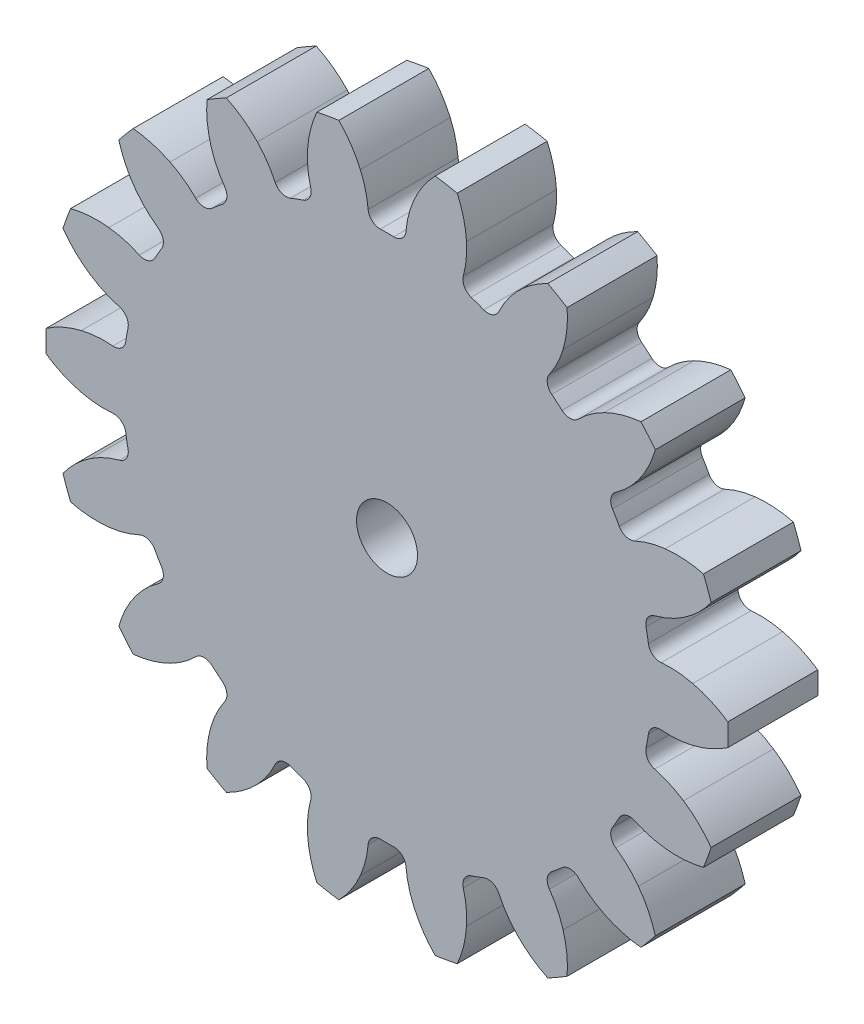
SolidWorks part; units mm, degrees
ref_plane "Front" through (0, 0, 0) normal (0, 0, 1) x (1, 0, 0)
ref_plane "Top" through (0, 0, 0) normal (0, 1, 0) x (1, 0, 0)
ref_plane "Right" through (0, 0, 0) normal (1, 0, 0) x (0, 0, -1)
sketch "Sketch1" plane through (0, 0, 0) normal (0, 0, 1) x (1, 0, 0)
  line L0 (0, 0) -> (19.939, 0) construction
  line L1 (19.939, 0) -> (22.1544, 0) construction
  circle A0 centre (0, 0) radius 19.939 construction
  circle A1 centre (0, 0) radius 22.1544
  dimension "pitch_diameter" = 39.878
  dimension "addendum" = 2.2154
extrude "GEAR_BASE" add sketch "Sketch1" along normal mid plane 5.842
sketch "Sketch2" plane through (0, 0, 2.921) normal (0, 0, 1) x (1, 0, 0)
  line L0 (0, 0) -> (17.1697, 0) construction
  line L1 (17.1697, 0) -> (19.939, 0) construction
  line L2 (0, 0) -> (-22.1544, 0) construction
  line L3 (0, 0) -> (-20.8184, -7.5773) construction
  line L4 (-21.0554, -6.8914) -> (-19.2602, -5.1582) construction
  line L5 (-19.2602, -5.1582) -> (-16.6935, -4.0158) construction
  line L6 (-22.1426, -0.7256) -> (-19.8629, -1.7402) construction
  line L7 (-19.8629, -1.7402) -> (-17.0602, -1.9359) construction
  line L8 (-18.665, -6.7935) -> (-19.2602, -5.1582) construction
  line L9 (-19.8629, -1.7402) -> (-19.8629, 0) construction
  line L12 (0, 0) -> (-19.8629, -1.7402) construction
  line L13 (0, 0) -> (-19.2602, -5.1582) construction
  line L14 (-19.2602, -5.1582) -> (-16.762, -14.4864) construction
  line L15 (-19.8629, -1.7402) -> (-20.7057, 7.8798) construction
  line L16 (-19.2602, -5.1582) -> (-19.8629, -1.7402) construction
  line L17 (-16.9088, -2.9815) -> (-17.0602, -1.9359) construction
  line L18 (-16.9088, -2.9815) -> (-16.6935, -4.0158) construction
  circle A0 centre (0, 0) radius 19.939 construction
  circle A1 centre (0, 0) radius 17.1697 construction
  circle A2 centre (0, 0) radius 22.1544 construction
  arc A3 (-21.0554, -6.8914) -> (-22.1426, -0.7256) centre (0, 0) cw
  arc A4 (-16.6935, -4.0158) -> (-17.0602, -1.9359) centre (0, 0) cw construction
  arc A6 (-21.0554, -6.8914) -> (-19.2602, -5.1582) centre (-15.4012, -10.9516) cw
  arc A7 (-22.1426, -0.7256) -> (-19.8629, -1.7402) centre (-18.2181, 5.0236) ccw
  arc A8 (-19.2602, -5.1582) -> (-17.3885, -4.3144) centre (-15.7761, -10.3888) cw
  arc A9 (-19.8629, -1.7402) -> (-17.8155, -1.893) centre (-18.3779, 4.3666) ccw
  arc A10 (-17.3885, -4.3144) -> (-16.8275, -3.4109) centre (-17.5874, -3.565) ccw
  arc A11 (-17.8155, -1.893) -> (-16.9793, -2.5501) centre (-17.7461, -2.6653) cw
  arc A12 (-16.8275, -3.4109) -> (-16.9793, -2.5501) centre (0, 0) cw
  dimension "base_fillet" = 0.7754
  dimension "D12" = 6.9609
  dimension "deddendum" = 2.7693
  dimension "D3" = 20
  dimension "D4" = 1.7402
  dimension "D5" = 1.7402
  dimension "D11" = 3.4707
  dimension "Pressure_Angle" = 20
  dimension "D14" = 9
  dimension "D15" = 9
extrude "GEAR_CUT" cut sketch "Sketch2" against normal through all
ref_axis "GEAR_AXIS" through (0, 0, 50) along (0, 0, -1)
pattern_circular "GEAR_TEETH" count 18 over 360 about axis through (0, 0, 50) along (0, 0, -1) of "GEAR_CUT"
sketch "Sketch5" plane through (0, 0, 2.921) normal (0, 0, -1) x (-1, 0, 0)
  circle A0 centre (0, 0) radius 1.9812
  dimension "bore" = 3.9624
extrude "BORE" cut sketch "Sketch5" along normal through all
sketch "Sketch4" plane through (0, 0, -2.921) normal (0, 0, 1) x (1, 0, 0)
  circle A0 centre (0, 0) radius 19.939
  circle A1 centre (0, 0) radius 1.9812
  circle A2 centre (0, 0) radius 1.9812 construction
  dimension "hub_diameter" = 39.878
extrude "HUB" [suppressed] add sketch "Sketch4" against normal blind 6.35
sketch "Sketch6" [suppressed] plane through (0, 0, 0) normal (0, 1, 0) x (1, 0, 0)
  line L0 (19.939, 4.7625) -> (0, 4.7625) construction
  line L1 (19.939, 1.5875) -> (19.939, 7.9375) construction
  line L2 (0, 4.7625) -> (-19.939, 4.7625) construction
  line L3 (-19.939, 7.9375) -> (-19.939, 1.5875) construction
  circle A0 centre (0, 4.7625) radius 0.7938
  dimension "sss_diam" = 1.5875
extrude "PINHOLE" [suppressed] cut sketch "Sketch6" along normal through all
equation "\"N_teeth\"=18.000000"
equation "\"pitch_diameter\"=1.57"
equation "\"Pd\"=\"N_teeth\"/\"pitch_diameter\""
equation "\"addendum\"=1.000/\"Pd\""
equation "\"face_width\"=0.23"
equation "\"deddendum\"=1.250/\"Pd\""
equation "\"D3@Sketch2\" = 360/\"N_teeth\""
equation "\"tooth_thickness\"=1.571/\"Pd\""
equation "\"D4@Sketch2\" = \"tooth_thickness\"/2"
equation "\"D5@Sketch2\" = \"tooth_thickness\"/2"
equation "\"Pressure_Angle\"=20.000000"
equation "\"base_fillet\"=0.35/\"Pd\""
equation "\"D12@Sketch2\" = 2*\"tooth_thickness\""
equation "\"hub_diameter\"=1.57"
equation "\"bore\"=0.156000"
equation "\"hub_projection\"=0.250000"
equation "\"sss_diam\"=0.062500"
